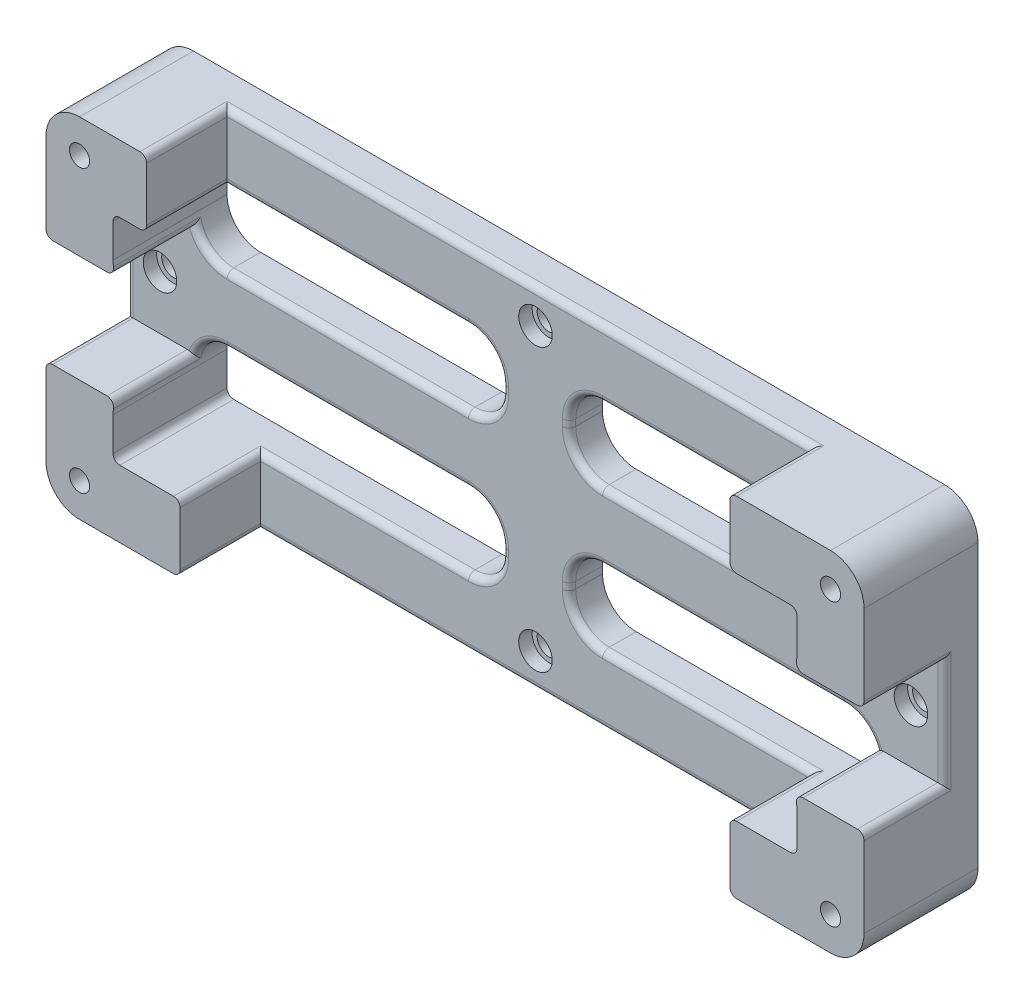
SolidWorks part; units mm, degrees
ref_plane "Front Plane" through (0, 0, 0) normal (0, 0, 1) x (1, 0, 0)
ref_plane "Top Plane" through (0, 0, 0) normal (0, 1, 0) x (1, 0, 0)
ref_plane "Right Plane" through (0, 0, 0) normal (1, 0, 0) x (0, 0, -1)
sketch "Sketch1" plane through (0, 0, 0) normal (0, 0, 1) x (1, 0, 0)
  line L0 (0, 0) -> (102, 0)
  line L1 (102, 0) -> (102, 32)
  line L2 (102, 32) -> (0, 32)
  line L3 (0, 32) -> (0, 0)
  line L4 (-10, -10) -> (112, -10)
  line L5 (112, -10) -> (112, 42)
  line L6 (112, 42) -> (-10, 42)
  line L7 (-10, 42) -> (-10, -10)
  dimension "D1" = 102
  dimension "D2" = 32
  dimension "D3" = 10
  dimension "D4" = 10
  dimension "D5" = 10
  dimension "D6" = 10
extrude "Boss-Extrude1" add sketch "Sketch1" along normal blind 5
sketch "Sketch2" plane through (0, 0, 5) normal (0, 0, 1) x (1, 0, 0)
  line L0 (51, 32) -> (56, 32)
  line L2 (102, 32) -> (0, 32) construction
  line L3 (51, 32) -> (46, 32)
  line L4 (0, 16) -> (0, 21)
  line L5 (0, 32) -> (0, 0) construction
  line L6 (0, 16) -> (0, 11)
  line L7 (51, 0) -> (56, 0)
  line L8 (0, 0) -> (102, 0) construction
  line L9 (51, 0) -> (46, 0)
  line L10 (102, 16) -> (102, 21)
  line L11 (102, 0) -> (102, 32) construction
  line L12 (102, 16) -> (102, 11)
  line L13 (46, 0) -> (46, 11)
  line L14 (46, 11) -> (0, 11)
  line L15 (0, 21) -> (46, 21)
  line L16 (46, 21) -> (46, 32)
  line L17 (56, 32) -> (56, 21)
  line L18 (56, 21) -> (102, 21)
  line L19 (102, 11) -> (56, 11)
  line L20 (56, 11) -> (56, 0)
  dimension "D1" = 5
  dimension "D2" = 5
  dimension "D3" = 5
  dimension "D4" = 5
  dimension "D5" = 5
  dimension "D6" = 5
  dimension "D7" = 5
  dimension "D8" = 5
extrude "Boss-Extrude2" add sketch "Sketch2" against normal blind 5
sketch "Sketch3" plane through (0, 0, 5) normal (0, 0, 1) x (1, 0, 0)
  line L0 (-10, 42) -> (5, 42)
  line L1 (112, 42) -> (-10, 42) construction
  line L2 (5, 42) -> (5, 32)
  line L3 (46, 32) -> (0, 32) construction
  line L4 (5, 32) -> (0, 32)
  line L5 (0, 32) -> (0, 24)
  line L6 (0, 32) -> (0, 21) construction
  line L7 (0, 24) -> (-10, 24)
  line L8 (-10, 42) -> (-10, -10) construction
  line L9 (-10, 24) -> (-10, 42)
  line L10 (-10, -10) -> (10, -10)
  line L11 (-10, -10) -> (112, -10) construction
  line L12 (10, -10) -> (10, 0)
  line L13 (0, 0) -> (46, 0) construction
  line L14 (10, 0) -> (0, 0)
  line L15 (0, 0) -> (0, 8)
  line L16 (0, 11) -> (0, 0) construction
  line L17 (0, 8) -> (-10, 8)
  line L18 (-10, 8) -> (-10, -10)
  line L19 (112, -10) -> (112, 8)
  line L20 (112, -10) -> (112, 42) construction
  line L21 (112, 8) -> (102, 8)
  line L22 (102, 0) -> (102, 11) construction
  line L23 (102, 8) -> (102, 0)
  line L24 (102, 0) -> (92, 0)
  line L25 (56, 0) -> (102, 0) construction
  line L26 (92, 0) -> (92, -10)
  line L27 (92, -10) -> (112, -10)
  line L28 (112, 42) -> (92, 42)
  line L31 (102, 32) -> (102, 24)
  line L32 (102, 21) -> (102, 32) construction
  line L33 (102, 24) -> (112, 24)
  line L34 (112, 24) -> (112, 42)
  line L35 (102, 32) -> (92, 32)
  line L36 (102, 32) -> (56, 32) construction
  line L37 (92, 32) -> (92, 42)
  dimension "D1" = 15
  dimension "D2" = 18
  dimension "D3" = 20
  dimension "D4" = 18
  dimension "D5" = 18
  dimension "D6" = 20
  dimension "D7" = 20
  dimension "D8" = 18
extrude "Boss-Extrude3" add sketch "Sketch3" along normal blind 12
sketch "Sketch4" plane through (0, 0, 17) normal (0, 0, 1) x (1, 0, 0)
  line L0 (112, -10) -> (112, 8) construction
  line L1 (92, -10) -> (112, -10) construction
  line L2 (112, 24) -> (112, 42) construction
  line L3 (112, 42) -> (92, 42) construction
  line L4 (-10, -10) -> (10, -10) construction
  line L5 (-10, 8) -> (-10, -10) construction
  line L6 (5, 42) -> (-10, 42) construction
  line L7 (-10, 42) -> (-10, 24) construction
  circle A0 centre (-5, 37) radius 1.5
  circle A1 centre (107, 37) radius 1.5
  circle A2 centre (107, -5) radius 1.5
  circle A3 centre (-5, -5) radius 1.5
  dimension "D1" = 3
  dimension "D2" = 3
  dimension "D3" = 3
  dimension "D4" = 3
  dimension "D5" = 5
  dimension "D6" = 5
  dimension "D7" = 5
  dimension "D8" = 5
  dimension "D9" = 5
  dimension "D10" = 5
  dimension "D11" = 5
  dimension "D12" = 5
extrude "Cut-Extrude1" cut sketch "Sketch4" against normal blind 7
sketch "Sketch5" plane through (0, 0, 5) normal (0, 0, 1) x (1, 0, 0)
  line L0 (46, 21) -> (0, 21) construction
  line L1 (46, 32) -> (46, 21) construction
  line L2 (102, 21) -> (56, 21) construction
  line L3 (46, 11) -> (46, 0) construction
  line L4 (-10, 24) -> (-10, 8) construction
  line L5 (112, 8) -> (112, 24) construction
  line L6 (10, -10) -> (92, -10) construction
  line L7 (92, 42) -> (5, 42) construction
  circle A0 centre (-5, 16) radius 1.75
  circle A1 centre (51, 37) radius 1.75
  circle A2 centre (107, 16) radius 1.75
  circle A3 centre (51, -5) radius 1.75
  dimension "D1" = 3.5
  dimension "D2" = 3.5
  dimension "D3" = 3.5
  dimension "D4" = 3.5
  dimension "D5" = 5
  dimension "D6" = 5
  dimension "D7" = 5
  dimension "D8" = 5
  dimension "D9" = 5
  dimension "D10" = 5
  dimension "D11" = 5
  dimension "D12" = 5
extrude "Cut-Extrude2" cut sketch "Sketch5" against normal through all
sketch "Sketch6" plane through (0, 0, 5) normal (0, 0, 1) x (1, 0, 0)
  circle A0 centre (-5, 16) radius 2.5
  circle A1 centre (51, 37) radius 2.5
  circle A2 centre (51, -5) radius 2.5
  circle A3 centre (107, 16) radius 2.5
  dimension "D1" = 5
  dimension "D2" = 5
  dimension "D3" = 5
  dimension "D4" = 5
extrude "Cut-Extrude3" cut sketch "Sketch6" against normal blind 2
fillet "Fillet1" radius 5 16 edges at (-10, 42, 8.5) (112, 42, 8.5) (112, -10, 8.5) (-10, -10, 8.5) (56, 11, 2.5) (56, 0, 2.5) (56, 21, 2.5) (102, 21, 2.5) (56, 32, 2.5) (102, 11, 2.5) (46, 0, 2.5) (46, 11, 2.5) (0, 11, 2.5) (0, 21, 2.5) (46, 32, 2.5) (46, 21, 2.5)
fillet "Fillet2" radius 1 48 edges at (76.5, 0, 5) (57.4645, 1.4645, 5) (99.7386, 10.1833, 5) (79, 11, 5) (57.4645, 9.5355, 5) (2.2614, 10.1833, 5) (23, 11, 5) (44.5355, 9.5355, 5) (25.5, 0, 5) (44.5355, 1.4645, 5) (99.7386, 21.8167, 5) (79, 21, 5) (57.4645, 22.4645, 5) (76.5, 32, 5) (57.4645, 30.5355, 5) (23, 32, 5) (44.5355, 30.5355, 5) (2.2614, 21.8167, 5) (23, 21, 5) (44.5355, 22.4645, 5) (92, 42, 11) (5, 32, 11) (5, 42, 11) (10, 0, 11) (10, -10, 11) (48.5, 42, 5) (51, -10, 5) (92, -10, 11) (92, 0, 11) (112, 8, 11) (112, 24, 11) (112, 16, 5) (56, 5.5, 5) (46, 5.5, 5) (56, 26.5, 5) (46, 26.5, 5) (92, 32, 11) (-10, 24, 11) (-10, 16, 5) (-10, 8, 11) (0, 0, 8.5) (102, 0, 8.5) (0, 32, 8.5) (102, 32, 8.5) (101.5826, 8, 11) (101.5826, 24, 11) (0.4174, 8, 11) (0.4174, 24, 11)
